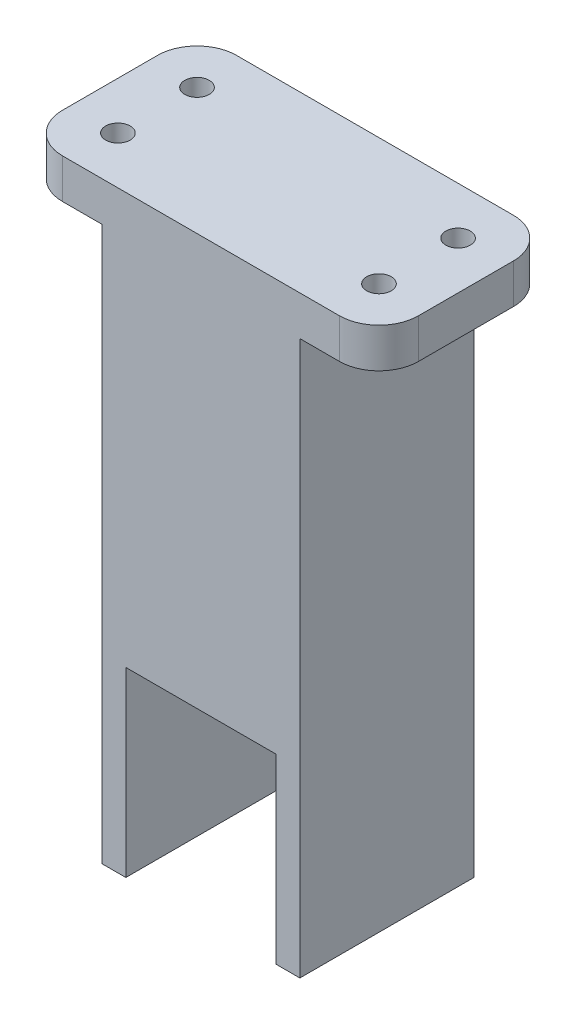
SolidWorks part; units mm, degrees
ref_plane "Alzado" through (0, 0, 0) normal (0, 0, 1) x (1, 0, 0)
ref_plane "Planta" through (0, 0, 0) normal (0, 1, 0) x (1, 0, 0)
ref_plane "Vista lateral" through (0, 0, 0) normal (1, 0, 0) x (0, 0, -1)
sketch "Croquis1" plane through (0, 0, 0) normal (0, 1, 0) x (1, 0, 0)
  circle A0 centre (0, 0) radius 10
  circle A1 centre (0, 0) radius 3.5
  dimension "D1" = 20
  dimension "D2" = 7
extrude "Extruir1" add sketch "Croquis1" along normal blind 12
sketch "Croquis2" plane through (0, 12, 0) normal (0, 1, 0) x (1, 0, 0)
  line L1 (22.5, 11) -> (-22.5, 11)
  line L2 (22.5, 11) -> (22.5, -11)
  line L3 (22.5, -11) -> (-22.5, -11)
  line L4 (-22.5, 11) -> (-22.5, -11)
  line L5 (22.5, 11) -> (-22.5, -11) construction
  line L6 (22.5, -11) -> (-22.5, 11) construction
  point P0 (0, 0)
  dimension "D1" = 45
  dimension "D2" = 22
extrude "Saliente-Extruir1" add sketch "Croquis2" along normal blind 5
fillet "Redondeo1" radius 5 1 edges at (22.5, 14.5, -11)
fillet "Redondeo2" radius 5 1 edges at (22.5, 14.5, 11)
fillet "Redondeo3" radius 5 1 edges at (-22.5, 14.5, 11)
fillet "Redondeo4" radius 5 1 edges at (-22.5, 14.5, -11)
sketch "Croquis3" plane through (0, 0, 0) normal (0, -1, 0) x (1, 0, 0)
  circle A0 centre (0, 0) radius 4.1
  dimension "D1" = 8.2
extrude "Cortar-Extruir1" cut sketch "Croquis3" against normal blind 45
sketch "Croquis4" plane through (0, 12, 0) normal (0, -1, 0) x (1, 0, 0)
  circle A0 centre (-16.5, 5) radius 1.55
  circle A1 centre (-16.5, -5) radius 1.55
  circle A2 centre (16.5, 5) radius 1.55
  circle A3 centre (16.5, -5) radius 1.55
extrude "Cortar-Extruir2" cut sketch "Croquis4" against normal blind 45
sketch "Croquis7" plane through (0, 0, 11) normal (0, 0, 1) x (1, 0, 0)
  line L0 (-17.5, 12) -> (17.5, 12) construction
  line L1 (11.057, -12) -> (-11.057, -12)
  line L2 (11.057, -12) -> (11.057, 12)
  line L3 (11.057, 12) -> (-11.057, 12)
  line L4 (-11.057, -12) -> (-11.057, 12)
  line L5 (11.057, -12) -> (-11.057, 12) construction
  line L6 (11.057, 12) -> (-11.057, -12) construction
  point P0 (0, 0)
extrude "Cortar-Extruir4" cut sketch "Croquis7" against normal blind 70
sketch "Croquis8" plane through (0, 12, 0) normal (0, -1, 0) x (1, 0, 0)
  line L1 (22.5, 11) -> (-22.5, 11)
  line L2 (22.5, 11) -> (22.5, -11)
  line L3 (22.5, -11) -> (-22.5, -11)
  line L4 (-22.5, 11) -> (-22.5, -11)
  line L5 (22.5, 11) -> (-22.5, -11) construction
  line L6 (22.5, -11) -> (-22.5, 11) construction
  point P0 (0, 0)
  dimension "D1" = 22
extrude "Saliente-Extruir2" add sketch "Croquis8" along normal blind 5
fillet "Redondeo5" radius 5 1 edges at (-22.5, 9.5, -11)
fillet "Redondeo6" radius 5 1 edges at (22.5, 9.5, -11)
fillet "Redondeo7" radius 5 1 edges at (22.5, 9.5, 11)
fillet "Redondeo8" radius 5 1 edges at (-22.5, 9.5, 11)
sketch "Croquis9" plane through (0, 17, 0) normal (0, 1, 0) x (1, 0, 0)
  circle A0 centre (-16.5, -5) radius 1.55
  circle A1 centre (-16.5, 5) radius 1.55
  circle A2 centre (16.5, -5) radius 1.55
  circle A3 centre (16.5, 5) radius 1.55
  circle A4 centre (0, 0) radius 4.1
extrude "Cortar-Extruir5" cut sketch "Croquis9" against normal blind 15
sketch "Croquis10" plane through (0, 17, 0) normal (0, 1, 0) x (1, 0, 0)
  line L1 (-5.6646, 5.9063) -> (5.6646, 5.9063)
  line L2 (-5.6646, 5.9063) -> (-5.6646, -5.9063)
  line L3 (-5.6646, -5.9063) -> (5.6646, -5.9063)
  line L4 (5.6646, 5.9063) -> (5.6646, -5.9063)
  line L5 (-5.6646, 5.9063) -> (5.6646, -5.9063) construction
  line L6 (-5.6646, -5.9063) -> (5.6646, 5.9063) construction
  point P0 (0, 0)
extrude "Saliente-Extruir3" add sketch "Croquis10" against normal blind 10
sketch "Croquis11" plane through (0, 0, -11) normal (0, 0, -1) x (-1, 0, 0)
  line L1 (-36.676, 12) -> (27.4693, 12)
  line L2 (-36.676, 12) -> (-36.676, 3.6337)
  line L3 (-36.676, 3.6337) -> (27.4693, 3.6337)
  line L4 (27.4693, 12) -> (27.4693, 3.6337)
extrude "Cortar-Extruir8" cut sketch "Croquis11" against normal blind 30
sketch "Croquis12" plane through (0, 12, 0) normal (0, -1, 0) x (1, 0, 0)
  line L0 (-17.5, -11) -> (17.5, -11) construction
  line L1 (-12.5, 11) -> (12.5, 11)
  line L2 (-12.5, 11) -> (-12.5, -11)
  line L3 (-12.5, -11) -> (12.5, -11)
  line L4 (12.5, 11) -> (12.5, -11)
  line L5 (-12.5, 11) -> (12.5, -11) construction
  line L6 (-12.5, -11) -> (12.5, 11) construction
  point P0 (0, 0)
  dimension "D1" = 25
extrude "Saliente-Extruir4" add sketch "Croquis12" along normal blind 70
sketch "Croquis13" plane through (0, -58, 0) normal (0, -1, 0) x (1, 0, 0)
  line L1 (-9.5, 8) -> (9.5, 8)
  line L2 (-9.5, 8) -> (-9.5, -8)
  line L3 (-9.5, -8) -> (9.5, -8)
  line L4 (9.5, 8) -> (9.5, -8)
  line L5 (-9.5, 8) -> (9.5, -8) construction
  line L6 (-9.5, -8) -> (9.5, 8) construction
  point P0 (0, 0)
extrude "Cortar-Extruir9" cut sketch "Croquis13" against normal blind 70
sketch "Croquis14" plane through (0, 0, 11) normal (0, 0, 1) x (1, 0, 0)
  line L0 (12.5, -58) -> (-12.5, -58) construction
  line L1 (-9.5, -35) -> (9.5, -35)
  line L2 (-9.5, -35) -> (-9.5, -58)
  line L3 (-9.5, -58) -> (9.5, -58)
  line L4 (9.5, -35) -> (9.5, -58)
  line L5 (-9.5, -35) -> (9.5, -58) construction
  line L6 (-9.5, -58) -> (9.5, -35) construction
  line L7 (-12.5, -58) -> (-12.5, 12) construction
  point P0 (0, -46.5)
  dimension "D1" = 19
  dimension "D2" = 12.5
  dimension "D3" = 23
extrude "Cortar-Extruir10" cut sketch "Croquis14" against normal blind 70
sketch "Croquis15" plane through (12.5, 0, 0) normal (1, 0, 0) x (0, 0, -1)
  line L0 (11, -58) -> (-11, -58) construction
  line L1 (-8, -58) -> (-24.823, -58)
  line L2 (-8, -58) -> (-8, -35)
  line L3 (-8, -35) -> (-24.823, -35)
  line L4 (-24.823, -58) -> (-24.823, -35)
  line L5 (11, -58) -> (11, 12) construction
  line L6 (8, -58) -> (22.3862, -58)
  line L7 (8, -58) -> (8, -35)
  line L8 (8, -35) -> (22.3862, -35)
  line L9 (22.3862, -58) -> (22.3862, -35)
  line L10 (-11, -58) -> (-11, 12) construction
  dimension "D1" = 23
  dimension "D2" = 23
  dimension "D3" = 3
  dimension "D4" = 3
extrude "Cortar-Extruir11" cut sketch "Croquis15" against normal blind 70
fillet "Redondeo9" radius 5 1 edges at (-11, -35, -8)
fillet "Redondeo10" radius 5 1 edges at (11, -35, -8)
fillet "Redondeo11" radius 5 1 edges at (-11, -35, 8)
fillet "Redondeo12" radius 5 1 edges at (11, -35, 8)
sketch "Croquis16" plane through (0, 12, 0) normal (0, -1, 0) x (1, 0, 0)
  line L0 (9.5, 8) -> (-9.5, 8) construction
  line L1 (1.5, -8) -> (-1.5, -8)
  line L2 (1.5, -8) -> (1.5, 8)
  line L3 (1.5, 8) -> (-1.5, 8)
  line L4 (-1.5, -8) -> (-1.5, 8)
  line L5 (1.5, -8) -> (-1.5, 8) construction
  line L6 (1.5, 8) -> (-1.5, -8) construction
  point P0 (0, 0)
  dimension "D1" = 3
extrude "Saliente-Extruir5" add sketch "Croquis16" along normal blind 47
sketch "Croquis17" plane through (12.5, 0, 0) normal (1, 0, 0) x (0, 0, -1)
  line L1 (-11, -35) -> (11, -35)
  line L2 (-11, -35) -> (-11, -58)
  line L3 (-11, -58) -> (11, -58)
  line L4 (11, -35) -> (11, -58)
  dimension "D1" = 22
  dimension "D2" = 23
extrude "Saliente-Extruir6" add sketch "Croquis17" against normal blind 3
sketch "Croquis18" plane through (-12.5, 0, 0) normal (-1, 0, 0) x (0, 0, 1)
  line L1 (-11, -35) -> (11, -35)
  line L2 (-11, -35) -> (-11, -58)
  line L3 (-11, -58) -> (11, -58)
  line L4 (11, -35) -> (11, -58)
  dimension "D1" = 23
  dimension "D2" = 22
extrude "Saliente-Extruir7" add sketch "Croquis18" against normal blind 3
